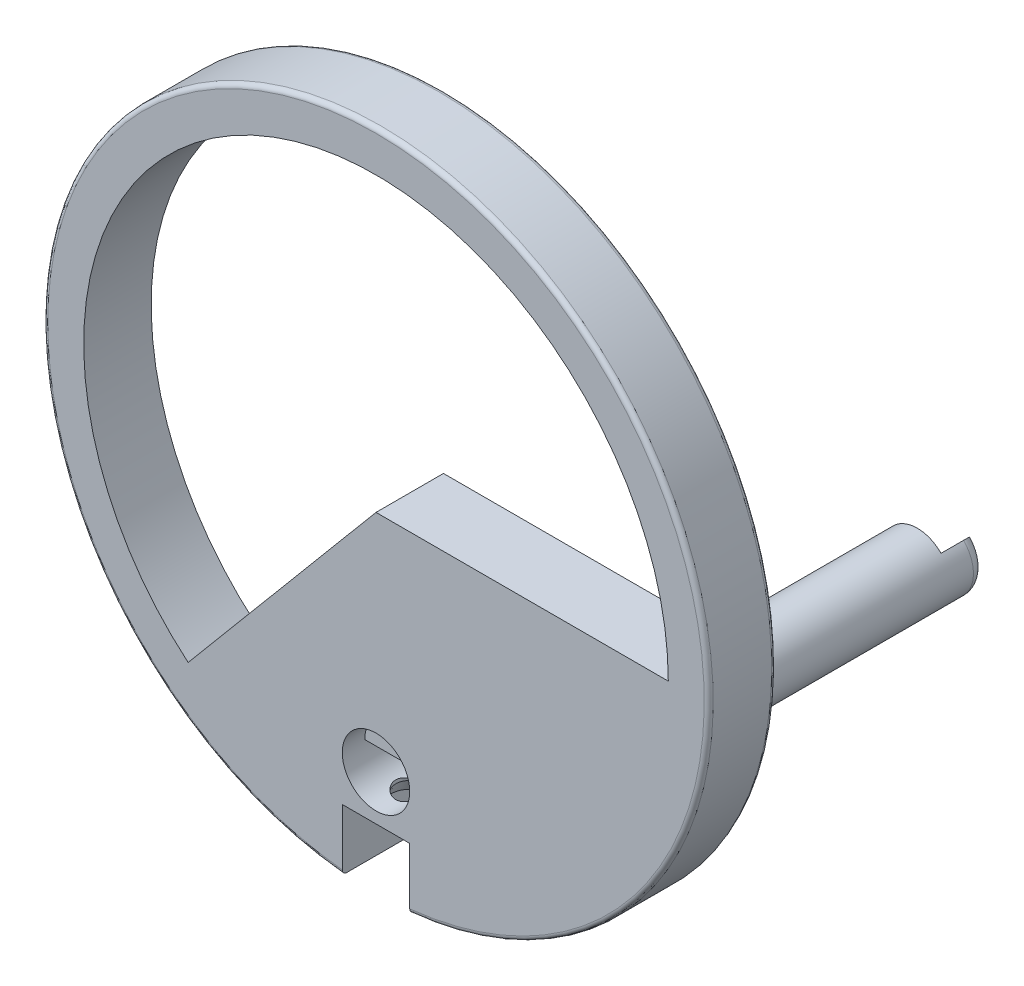
SolidWorks part; units mm, degrees
ref_plane "Front Plane" through (0, 0, 0) normal (0, 0, 1) x (1, 0, 0)
ref_plane "Top Plane" through (0, 0, 0) normal (0, 1, 0) x (1, 0, 0)
ref_plane "Right Plane" through (0, 0, 0) normal (1, 0, 0) x (0, 0, -1)
sketch "Esquisse2" plane through (0, 0, 2) normal (0, 0, -1) x (-1, 0, 0)
  circle A0 centre (0, -2) radius 14.7982
  dimension "D1" = 29.5964
extrude "Boss.-Extru.1" add sketch "Esquisse2" along normal blind 3
fillet "Congé2" radius 0.2 1 edges at (-14.7982, -2, -1)
fillet "Congé3" radius 0.2 1 edges at (-14.7982, -2, 2)
sketch "Esquisse11" plane through (0, 0, -1) normal (0, 0, -1) x (-1, 0, 0)
  line L29 (0, -2) -> (8.3562, -11.9586)
  line L36 (-13, -2) -> (0, -2)
  line L37 (0, -2) -> (0, -14) construction
  line L40 (-1.5, -14) -> (1.5, -14)
  line L42 (-1.5, -18.4679) -> (1.5, -18.4679)
  line L43 (1.5, -14) -> (1.5, -18.4679)
  line L44 (-1.5, -14) -> (-1.5, -18.4679)
  line L45 (0, -18.4679) -> (0, -21.2013) construction
  arc A22 (13, -2) -> (-13, -2) centre (0, -2) ccw
  arc A23 (13, -2) -> (8.3562, -11.9586) centre (0, -2) cw
  dimension "D1" = 26
  dimension "D2" = 130
  dimension "D4" = 12
extrude "Enlèv. mat.-Extru.3" cut sketch "Esquisse11" against normal up to next
sketch "Esquisse15" plane through (0, 0, 2) normal (0, 0, 1) x (1, 0, 0)
  line L0 (0, -2) -> (0, 8) construction
  line L1 (0, -2) -> (-3.0275, -2) construction
  circle A1 centre (0, -12) radius 1.5
  dimension "D2" = 3
  dimension "D1" = 10
extrude "Enlèv. mat.-Extru.5" cut sketch "Esquisse15" against normal blind 1
sketch "Esquisse22" plane through (0, 0, 1) normal (0, 0, 1) x (1, 0, 0)
  line L0 (-1.5, -12) -> (1.5, -12)
  circle A0 centre (0, -12) radius 1.5 construction
  arc A1 (-1.5, -12) -> (1.5, -12) centre (0, -12) ccw
extrude "Enlèv. mat.-Extru.8" cut sketch "Esquisse22" against normal blind 1.5
sketch "Esquisse23" plane through (0, 0, -1) normal (0, 0, -1) x (-1, 0, 0)
  line L0 (-14.5982, -2) -> (0, -2) construction
  line L1 (0, -2) -> (0, -18.3349) construction
  line L2 (0, -2) -> (-12.6428, -14.6428) construction
  circle A0 centre (0, -2) radius 14.5982 construction
  circle A1 centre (-7.0711, -9.0711) radius 2
  dimension "D3" = 4
  dimension "D1" = 45
  dimension "D2" = 10
extrude "Boss.-Extru.5" add sketch "Esquisse23" along normal blind 2.5
fillet "Congé4" radius 0.2 1 edges at (5.0711, -9.0711, -3.5)
sketch "Esquisse24" plane through (0, 0, -3.5) normal (0, 0, -1) x (-1, 0, 0)
  circle A0 centre (-7.0711, -9.0711) radius 1.5
  dimension "D1" = 3
extrude "Boss.-Extru.6" add sketch "Esquisse24" along normal blind 13
fillet "Congé5" radius 0.5 1 edges at (5.5711, -9.0711, -16.5)
sketch "Esquisse26" plane through (0, 0, -16.5) normal (0, 0, -1) x (-1, 0, 0)
  line L0 (-7.0711, -9.0711) -> (-4.4491, -9.0711) construction
  line L1 (-7.0711, -9.0711) -> (-4.9904, -11.1517) construction
  line L2 (-7.0711, -9.0711) -> (-5.5812, -10.5609)
  line L3 (-5.5812, -10.5609) -> (-3.8609, -8.8405)
  line L4 (-3.8609, -8.8405) -> (-6.8522, -5.8492)
  line L5 (-6.8522, -5.8492) -> (-8.5726, -7.5696)
  line L6 (-8.5726, -7.5696) -> (-7.0711, -9.0711)
  dimension "D1" = 2.433
  dimension "D2" = 4.2304
  dimension "D3" = 45
extrude "Enlèv. mat.-Extru.9" cut sketch "Esquisse26" against normal blind 1.5
hole_wizard "Trou taraudé M1.61" positions "Esquisse28" profile "Esquisse29" tap size "M1.6" standard "ISO" end condition up to next
sketch "Esquisse28" plane through (0, -14, 0) normal (0, -1, 0) x (-1, 0, 0)
  line L0 (1.5, 1) -> (-1.5, 1) construction
  point P0 (0, -0.5)
  dimension "D1" = 1.5
sketch "Esquisse29" plane through (0, -14, 0.5) normal (1, 0, 0) x (0, 0, -1)
  line L0 (0, 0) -> (0, 0.5)
  line L1 (0, 0.5) -> (0.625, 0.5)
  line L2 (0.625, 0.5) -> (0.625, 0.4828)
  line L3 (0.625, 0.4828) -> (0.825, 0)
  line L5 (0.825, 0) -> (0, 0)
  line L6 (-0.625, 0.4828) -> (-0.825, 0) construction
  line L11 (0, -6.35) -> (0, 107.95) construction
  dimension "Diamètre du trou pour taraudage jusqu'au prochain" = 1.25
  dimension "Profondeur du trou pour taraudage jusqu'au prochain" = 0.5
  dimension "Diamètre du fraisage entrant" = 1.65
  dimension "Angle du fraisage entrant" = 45
